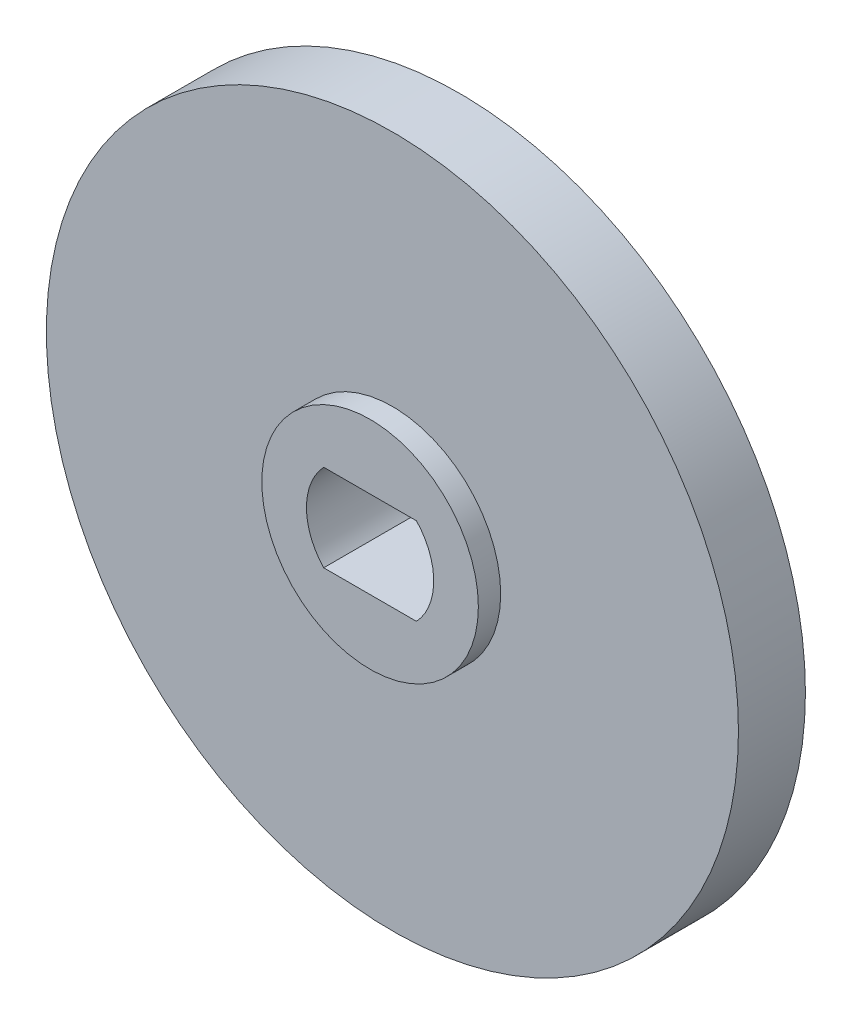
SolidWorks part; units mm, degrees
ref_plane "Front Plane" through (0, 0, 0) normal (0, 0, 1) x (1, 0, 0)
ref_plane "Top Plane" through (0, 0, 0) normal (0, 1, 0) x (1, 0, 0)
ref_plane "Right Plane" through (0, 0, 0) normal (1, 0, 0) x (0, 0, -1)
sketch "Sketch1" plane through (0, 0, 0) normal (0, 0, 1) x (1, 0, 0)
  circle A0 centre (0, 0) radius 15.5 construction
  circle A1 centre (0, 0) radius 15.5
extrude "Boss-Extrude1" add sketch "Sketch1" along normal blind 3
sketch "Sketch2" plane through (0, 0, 0) normal (0, 0, -1) x (-1, 0, 0)
  line L0 (-7.8174, 8.129) -> (-3.5527, 4.927)
  line L1 (0.2749, 6.0681) -> (2.0901, 11.0826)
  line L2 (-7.8774, 8.0491) -> (-3.6127, 4.8471)
  line L3 (0.3689, 6.0341) -> (2.1842, 11.0485)
  line L4 (-7.8774, 8.0491) -> (-3.6127, 4.8471) construction
  line L5 (0.3689, 6.0341) -> (2.1842, 11.0485) construction
  arc A0 (1.3416, 12.2836) -> (-7.8486, 9.5439) centre (0, 0) ccw
  arc A1 (-7.8486, 9.5439) -> (-7.8174, 8.129) centre (-7.277, 8.8488) ccw
  arc A2 (-3.5527, 4.927) -> (-2.5887, 4.8527) centre (-3.0123, 5.6468) ccw
  arc A3 (-0.491, 5.478) -> (-2.5887, 4.8527) centre (0, 0) ccw
  arc A4 (-0.491, 5.478) -> (0.2749, 6.0681) centre (-0.5714, 6.3744) ccw
  arc A5 (2.0901, 11.0826) -> (1.3416, 12.2836) centre (1.2439, 11.3889) ccw
  arc A6 (1.3524, 12.383) -> (-7.9122, 9.6211) centre (0, 0) ccw
  arc A7 (-7.9122, 9.6211) -> (-7.8774, 8.0491) centre (-7.277, 8.8488) ccw
  arc A8 (-3.6127, 4.8471) -> (-2.5416, 4.7645) centre (-3.0123, 5.6468) ccw
  arc A9 (-0.4821, 5.3784) -> (-2.5416, 4.7645) centre (0, 0) ccw
  arc A10 (-0.4821, 5.3784) -> (0.3689, 6.0341) centre (-0.5714, 6.3744) ccw
  arc A11 (2.1842, 11.0485) -> (1.3524, 12.383) centre (1.2439, 11.3889) ccw
  arc A12 (1.3524, 12.383) -> (-7.9122, 9.6211) centre (0, 0) ccw construction
  arc A13 (-7.9122, 9.6211) -> (-7.8774, 8.0491) centre (-7.277, 8.8488) ccw construction
  arc A14 (-3.6127, 4.8471) -> (-2.5416, 4.7645) centre (-3.0123, 5.6468) ccw construction
  arc A15 (-0.4821, 5.3784) -> (-2.5416, 4.7645) centre (0, 0) ccw construction
  arc A16 (-0.4821, 5.3784) -> (0.3689, 6.0341) centre (-0.5714, 6.3744) ccw construction
  arc A17 (2.1842, 11.0485) -> (1.3524, 12.383) centre (1.2439, 11.3889) ccw construction
  dimension "D1" = 0
  dimension "D2" = 0.1
extrude "Boss-Extrude2" add sketch "Sketch2" along normal offset from surface (1.9 mm away) 0.3
pattern_circular "CirPattern1" count 5 over 360 about axis through (0, 0, 3) along (0, 0, -1) of "Boss-Extrude2"
sketch "Sketch3" plane through (0, 0, 0) normal (0, 0, 1) x (1, 0, 0)
  circle A0 centre (0, 0) radius 4.85
  dimension "D1" = 9.7
extrude "Boss-Extrude3" add sketch "Sketch3" along normal blind 1 from surface starting at face at (15.5, 0, 3)
sketch "Sketch4" plane through (0, 0, 0) normal (0, 0, 1) x (1, 0, 0)
  circle A0 centre (0, 0) radius 2
  dimension "D1" = 4
extrude "Cut-Extrude1" [suppressed] cut sketch "Sketch4" along normal through all
sketch "Sketch5" plane through (0, 0, 4) normal (0, 0, 1) x (1, 0, 0)
  line L0 (-2.0785, 1.95) -> (2.0785, 1.95)
  line L1 (2.0785, -1.95) -> (-2.0785, -1.95)
  arc A0 (-2.0785, 1.95) -> (-2.0785, -1.95) centre (0, 0) ccw
  arc A1 (2.0785, -1.95) -> (2.0785, 1.95) centre (0, 0) ccw
  dimension "D1" = 5.7
  dimension "D2" = 3.9
extrude "Cut-Extrude2" cut sketch "Sketch5" against normal through all
sketch "Sketch6" plane through (0, 0, 0) normal (0, 0, -1) x (-1, 0, 0)
  circle A1 centre (0, 0) radius 15.5 construction
  circle A2 centre (0, 0) radius 15.5
  circle A3 centre (0, 0) radius 13.5
  dimension "D1" = 2
extrude "Boss-Extrude4" [suppressed] add sketch "Sketch6" along normal offset from surface (0.9 mm away) 0.1
